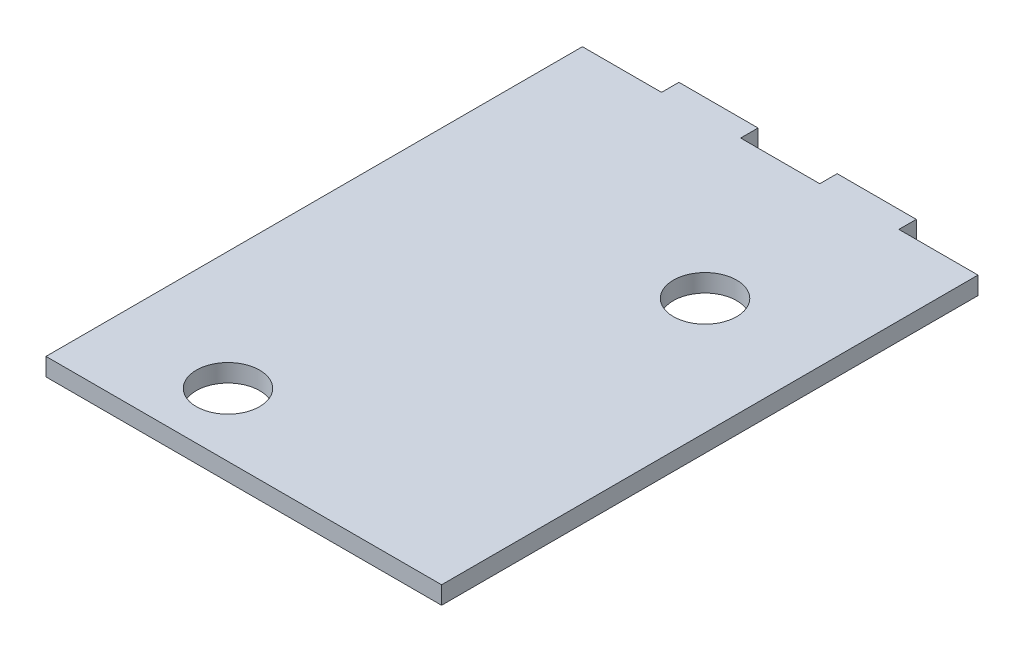
SolidWorks part; units mm, degrees
ref_plane "Front Plane" through (0, 0, 0) normal (0, 0, 1) x (1, 0, 0)
ref_plane "Top Plane" through (0, 0, 0) normal (0, 1, 0) x (1, 0, 0)
ref_plane "Right Plane" through (0, 0, 0) normal (1, 0, 0) x (0, 0, -1)
sketch "Sketch2" plane through (0, 0, 0) normal (0, 1, 0) x (1, 0, 0)
  line L3 (110, 70) -> (-110, 70)
  line L4 (110, 70) -> (110, -70)
  line L5 (110, -70) -> (-110, -70)
  line L6 (-110, 70) -> (-110, -70)
  line L7 (110, 70) -> (-110, -70) construction
  line L8 (110, -70) -> (-110, 70) construction
  point P0 (0, 0)
  dimension "D1" = 220
  dimension "D2" = 140
extrude "Boss-Extrude1" add sketch "Sketch2" along normal blind 4.5
chamfer "Chamfer1" [suppressed] distance 75 angle 40
sketch "Sketch3" plane through (0, 4.5, 0) normal (0, 1, 0) x (1, 0, 0)
  line L0 (0, 70) -> (0, -54) construction
  line L1 (110, 70) -> (-110, 70) construction
  line L2 (0, -54) -> (40.6, -54) construction
  line L3 (40.6, -54) -> (40.6, 26) construction
  circle A0 centre (0, -54) radius 8
  circle A1 centre (40.6, 26) radius 8
  dimension "D2" = 16
  dimension "D5" = 16
  dimension "D1" = 124
  dimension "D3" = 80
  dimension "D4" = 40.6
extrude "Cut-Extrude1" cut sketch "Sketch3" against normal through all
sketch "Sketch4" plane through (0, 0, 0) normal (0, -1, 0) x (1, 0, 0)
  line L0 (110, 70) -> (110, -70) construction
  line L1 (110, -70) -> (90, -70)
  line L2 (110, -70) -> (110, -65.6)
  line L3 (110, -65.6) -> (90, -65.6)
  line L4 (90, -70) -> (90, -65.6)
  line L5 (110, -70) -> (90, -65.6) construction
  line L6 (110, -65.6) -> (90, -70) construction
  line L7 (0, -70) -> (0, 0) construction
  line L8 (70, -70) -> (50, -70)
  line L9 (70, -70) -> (70, -65.6)
  line L10 (70, -65.6) -> (50, -65.6)
  line L11 (50, -70) -> (50, -65.6)
  line L12 (70, -70) -> (50, -65.6) construction
  line L13 (70, -65.6) -> (50, -70) construction
  line L14 (30, -70) -> (10, -70)
  line L15 (30, -70) -> (30, -65.6)
  line L16 (30, -65.6) -> (10, -65.6)
  line L17 (10, -70) -> (10, -65.6)
  line L18 (30, -70) -> (10, -65.6) construction
  line L19 (30, -65.6) -> (10, -70) construction
  line L20 (-30, -65.6) -> (-10, -70) construction
  line L21 (-30, -70) -> (-10, -65.6) construction
  line L22 (-70, -65.6) -> (-50, -70) construction
  line L23 (-70, -70) -> (-50, -65.6) construction
  line L24 (-110, -65.6) -> (-90, -70) construction
  line L25 (-110, -70) -> (-90, -65.6) construction
  line L26 (-10, -70) -> (-10, -65.6)
  line L27 (-30, -65.6) -> (-10, -65.6)
  line L28 (-30, -70) -> (-30, -65.6)
  line L29 (-30, -70) -> (-10, -70)
  line L30 (-50, -70) -> (-50, -65.6)
  line L31 (-70, -65.6) -> (-50, -65.6)
  line L32 (-70, -70) -> (-70, -65.6)
  line L33 (-70, -70) -> (-50, -70)
  line L34 (-90, -70) -> (-90, -65.6)
  line L35 (-110, -65.6) -> (-90, -65.6)
  line L36 (-110, -70) -> (-110, -65.6)
  line L37 (-110, -70) -> (-90, -70)
  line L38 (0, -70) -> (110, -70) construction
  point P4 (100, -67.8)
  point P29 (-100, -67.8)
  dimension "D1" = 4.4
  dimension "D2" = 20
  dimension "D3" = 3
  dimension "D4" = 70
  dimension "D5" = 20
extrude "Teeth cut" cut sketch "Sketch4" against normal through all
sketch "Sketch5" plane through (0, 0, 0) normal (0, -1, 0) x (1, 0, 0)
  line L0 (-110, 70) -> (110, 70) construction
  line L1 (110, -70.1) -> (70, -70.1)
  line L2 (110, -70.1) -> (110, 70)
  line L3 (110, 70) -> (70, 70)
  line L4 (70, -70.1) -> (70, 70)
  line L5 (110, -70.1) -> (70, 70) construction
  line L6 (110, 70) -> (70, -70.1) construction
  line L7 (-110, -65.6) -> (-110, 70) construction
  line L8 (-30, -70.1) -> (-110, -70.1)
  line L9 (-30, -70.1) -> (-30, 70)
  line L10 (-30, 70) -> (-110, 70)
  line L11 (-110, -70.1) -> (-110, 70)
  line L12 (-30, -70.1) -> (-110, 70) construction
  line L13 (-30, 70) -> (-110, -70.1) construction
  line L14 (110, 70) -> (110, -65.6) construction
  point P4 (90, -0.05)
  point P11 (-70, -0.05)
  dimension "D1" = 80
  dimension "D2" = 40
extrude "Trim cut" cut sketch "Sketch5" against normal through all
